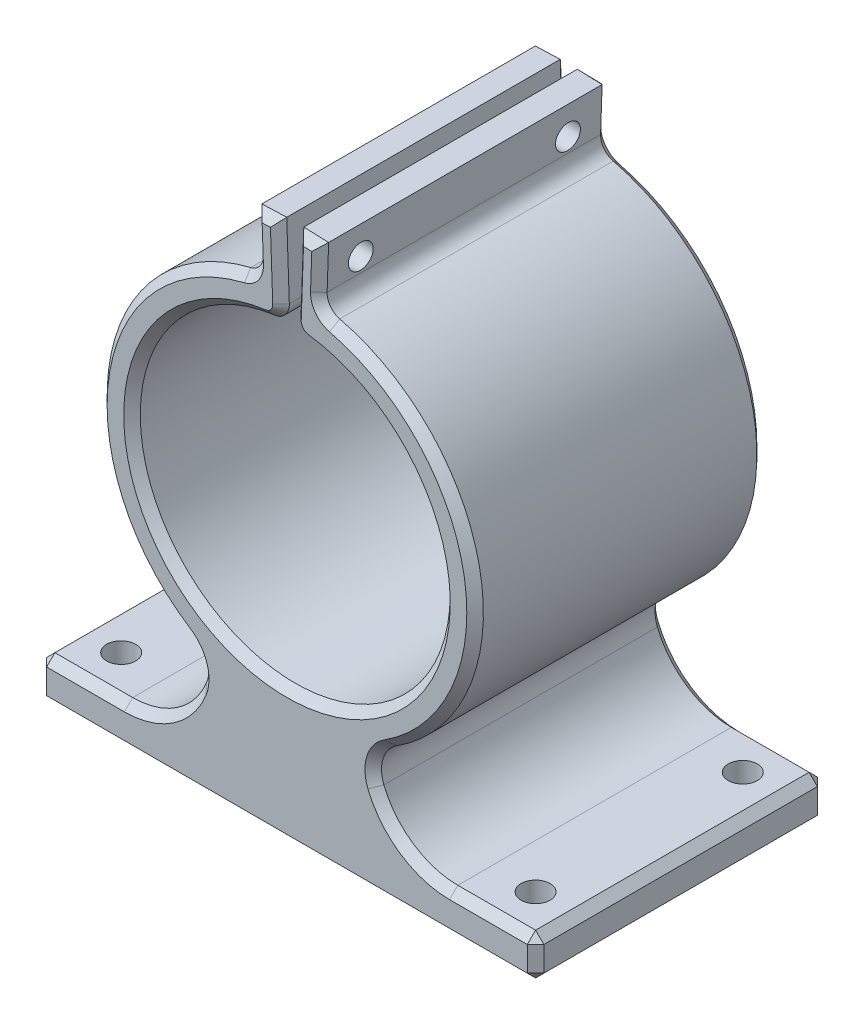
SolidWorks part; units mm, degrees
ref_plane "Front Plane" through (0, 0, 0) normal (0, 0, 1) x (1, 0, 0)
ref_plane "Top Plane" through (0, 0, 0) normal (0, 1, 0) x (1, 0, 0)
ref_plane "Right Plane" through (0, 0, 0) normal (1, 0, 0) x (0, 0, -1)
sketch "Sketch1" plane through (0, 0, 0) normal (0, 0, 1) x (1, 0, 0)
  line L0 (0, 0) -> (0, -35)
  line L1 (-30, -35) -> (30, -35)
  line L2 (30, -35) -> (30, -30)
  line L3 (0, 0) -> (0.7922, 22.6862)
  line L4 (30, -30) -> (19.6213, -30)
  line L5 (10, -20.3787) -> (10, -15.8016)
  line L6 (-30, -35) -> (-30, -30)
  line L7 (-30, -30) -> (-19.6213, -30)
  line L8 (-10, -20.3787) -> (-10, -15.8016)
  line L9 (0, 0) -> (-0.7922, 22.6862)
  line L10 (0.7922, 22.6862) -> (1.0296, 29.4829)
  line L11 (1.0296, 29.4829) -> (4.0277, 29.3782)
  line L12 (4.0277, 29.3782) -> (3.7834, 22.3825)
  line L13 (-0.7922, 22.6862) -> (-1.0296, 29.4829)
  line L14 (-1.0296, 29.4829) -> (-4.0277, 29.3782)
  line L15 (-4.0277, 29.3782) -> (-3.7834, 22.3825)
  arc A0 (-0.6526, 18.6886) -> (0.6526, 18.6886) centre (0, 0) ccw
  arc A1 (-0.7922, 22.6862) -> (0.7922, 22.6862) centre (0, 0) ccw
  arc A2 (19.6213, -30) -> (10, -20.3787) centre (19.6213, -20.3787) cw
  arc A3 (-19.6213, -30) -> (-10, -20.3787) centre (-19.6213, -20.3787) ccw
  dimension "D1" = 37.4
  dimension "D2" = 4
  dimension "D4" = 35
  dimension "D3" = 178
  dimension "D5" = 5
  dimension "D6" = 30
  dimension "D7" = 10
  dimension "D8" = 3
  dimension "D9" = 7
extrude "Boss-Extrude1" add sketch "Sketch1" along normal blind 35 contours L9 A1 L8 A0 | L8 A1 L0 A0 | L0 A1 L5 A0 | L5 A1 L3 A0 | L4 A2 A1 L0 L1 L2 | A3 L7 L6 L1 L0 A1 | A1 L13 L14 L15 | A1 L12 L11 L10 region at (5.1101, -19.8237, 0) region at (-5.1101, -19.8237, 0) region at (1.2059, 20.6705, 0) region at (-18.5159, 5.0181, 0) region at (11.633, -30.0214, 0) region at (-11.633, -30.0214, 0) region at (2.4161, 25.9986, 0) region at (-2.4161, 25.9986, 0)
sketch "Sketch2" plane through (0, 0, 0) normal (1, 0, 0) x (0, 0, -1)
  line L0 (-35, 29.3782) -> (-35, 22.3825) construction
  line L1 (-35, 29.3782) -> (-35, 22.3825)
  line L2 (-35, 25.8804) -> (0, 25.8804) construction
  line L3 (0, 29.3782) -> (0, 22.3825) construction
  circle A0 centre (-30, 25.8804) radius 1.5
  circle A1 centre (-5, 25.8804) radius 1.5
  dimension "D1" = 3
  dimension "D2" = 5
  dimension "D3" = 5
extrude "Cut-Extrude1" cut sketch "Sketch2" against normal through all both and the other way through all contours L2 A1 | L2 A0 | A0 L2 | A1 L2 region at (0, 26.517, 30) region at (0, 26.517, 5) region at (0, 25.2437, 5) region at (0, 25.2437, 30)
sketch "Sketch3" plane through (0, -30, 0) normal (0, 1, 0) x (1, 0, 0)
  line L8 (25, -5) -> (-25, -5)
  line L9 (25, -30) -> (25, -5)
  line L10 (-25, -30) -> (25, -30)
  line L11 (-25, -5) -> (-25, -30)
  line L12 (25, -5) -> (-25, -5) construction
  line L13 (25, -30) -> (25, -5) construction
  line L14 (-25, -30) -> (25, -30) construction
  line L15 (-25, -5) -> (-25, -30) construction
  circle A0 centre (-25, -5) radius 1.75
  circle A1 centre (-25, -30) radius 1.75
  circle A2 centre (25, -30) radius 1.75
  circle A3 centre (25, -5) radius 1.75
  dimension "D2" = 3.5
  dimension "D1" = 5
extrude "Cut-Extrude2" cut sketch "Sketch3" against normal through all
fillet "Fillet1" radius 4 2 edges at (-10, -20.3787, 17.5) (10, -20.3787, 17.5)
fillet "Fillet2" radius 2 4 edges at (3.7834, 22.3825, 17.5) (-0.6526, 18.6886, 17.5) (0.6526, 18.6886, 17.5) (-3.7834, 22.3825, 17.5)
chamfer "Chamfer1" distance 1 angle 45 48 edges at (30, -32.5, 0) (24.8107, -30, 0) (14.2372, -28.3525, 0) (3.935, 26.7237, 0) (2.5287, 29.4306, 0) (0.8743, 25.0368, 0) (0, -18.7, 0) (-0.8743, 25.0368, 0) (-2.5287, 29.4306, 0) (-3.935, 26.7237, 0) (-14.2372, -28.3525, 0) (-24.8107, -30, 0) (-30, -32.5, 0) (0, -35, 0) (-30, -32.5, 35) (-24.8107, -30, 35) (-14.2372, -28.3525, 35) (-3.935, 26.7237, 35) (-2.5287, 29.4306, 35) (-0.8743, 25.0368, 35) (0, -18.7, 35) (0.8743, 25.0368, 35) (2.5287, 29.4306, 35) (3.935, 26.7237, 35) (14.2372, -28.3525, 35) (24.8107, -30, 35) (30, -32.5, 35) (0, -35, 35) (-4.2472, 22.7913, 0) (-22.3894, 3.7421, 0) (-10.5966, -21.2632, 0) (10.5966, -21.2632, 0) (22.3894, 3.7421, 0) (4.2472, 22.7913, 0) (1.1909, 19.2291, 0) (-1.1909, 19.2291, 0) (1.1909, 19.2291, 35) (4.2472, 22.7913, 35) (22.3894, 3.7421, 35) (10.5966, -21.2632, 35) (-10.5966, -21.2632, 35) (-22.3894, 3.7421, 35) (-4.2472, 22.7913, 35) (-1.1909, 19.2291, 35) (-30, -30, 17.5) (-30, -35, 17.5) (30, -35, 17.5) (30, -30, 17.5)
